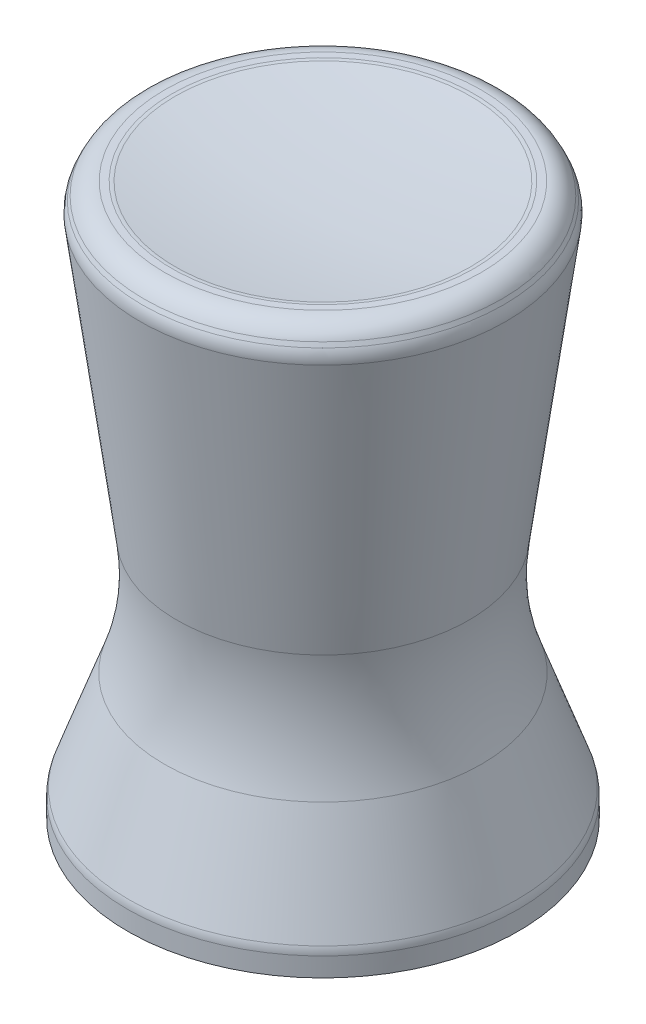
SolidWorks part; units mm, degrees
ref_plane "Front Plane" through (0, 0, 0) normal (0, 0, 1) x (1, 0, 0)
ref_plane "Top Plane" through (0, 0, 0) normal (0, 1, 0) x (1, 0, 0)
ref_plane "Right Plane" through (0, 0, 0) normal (1, 0, 0) x (0, 0, -1)
sketch "Sketch1" plane through (0, 0, 0) normal (0, 0, 1) x (1, 0, 0)
  line L0 (0, 0) -> (8.5, 0)
  line L1 (8.5, 0) -> (8.5, 1)
  line L2 (8.5, 1) -> (6, 8)
  line L3 (6, 8) -> (8, 23)
  line L4 (8, 23) -> (7.5, 24)
  line L5 (7.5, 24) -> (6.5, 24)
  line L6 (6.5, 24) -> (3.2692, 23.5) construction
  line L7 (0, 23.5) -> (0, 0) construction
  line L8 (0, 0) -> (0, 23.5)
  line L9 (3.2692, 23.5) -> (0, 23.5) construction
  spline S0 degree 2 poles (6.5, 24) (3.2692, 23.5) (0, 23.5) knots 0 0 0 1 1 1
  dimension "D1" = 24
  dimension "D2" = 8
  dimension "D3" = 1
  dimension "D4" = 8
  dimension "D5" = 1
  dimension "D6" = 0.5
  dimension "D7" = 0.5
  dimension "D8" = 1
  dimension "D9" = 8.5
  dimension "D10" = 6
revolve "Revolve1" add sketch "Sketch1" angle 360 about L7
fillet "Fillet1" radius 11 1 edges at (-6, 8, 0)
fillet "Fillet2" radius 1 4 edges at (-6.5, 24, 0) (-7.5, 24, 0) (-8, 23, 0) (-8.5, 1, 0)
sketch "Sketch3" plane through (0, 0, 0) normal (0, 0, 1) x (1, 0, 0)
  line L0 (0, 0) -> (3.875, 0)
  line L1 (-8.5, 0) -> (8.5, 0) construction
  line L2 (3.875, 0) -> (3.875, 6.5)
  line L3 (3.875, 6.5) -> (3.05, 7.325)
  line L4 (3.05, 7.325) -> (3.05, 17.75)
  line L5 (3.05, 17.75) -> (0, 17.75)
  line L6 (0, 17.75) -> (0, 0)
  dimension "D1" = 17.75
  dimension "D2" = 3.875
  dimension "D3" = 45
  dimension "D4" = 3.05
  dimension "D5" = 6.5
revolve "Cut-Revolve1" cut sketch "Sketch3" angle 360 about L6
ref_plane "Plane1" through (0, 7.325, 0) normal (0, 1, 0) x (1, 0, 0)
sketch "Sketch4" plane through (0, 17.75, 0) normal (0, -1, 0) x (1, 0, 0)
  line L0 (-2.6557, 1.5) -> (2.6557, 1.5)
  line L5 (-999.8551, -3) -> (49000.1449, -3) construction
  arc A7 (-0.1, -3.0484) -> (0.1, -3.0484) centre (0, 0) ccw
  arc A9 (0.1, -3.0484) -> (-0.1, -3.0484) centre (0, -3.05) ccw
  arc A10 (2.6557, 1.5) -> (-2.6557, 1.5) centre (0, 0) ccw
  circle A11 centre (0, 0) radius 3.05 construction
  point P1 (-1.8297, 1.5)
  point P10 (0, 0)
  point P11 (0, 0)
  dimension "D1" = 3
  dimension "D3" = 0.2
  dimension "D2" = 4.5
extrude "Boss-Extrude1" add sketch "Sketch4" along normal up to surface (10.425 mm away) up to plane "Plane1"
chamfer "Chamfer1" distance 0.35 angle 45 1 edges at (0, 7.325, 1.5)
